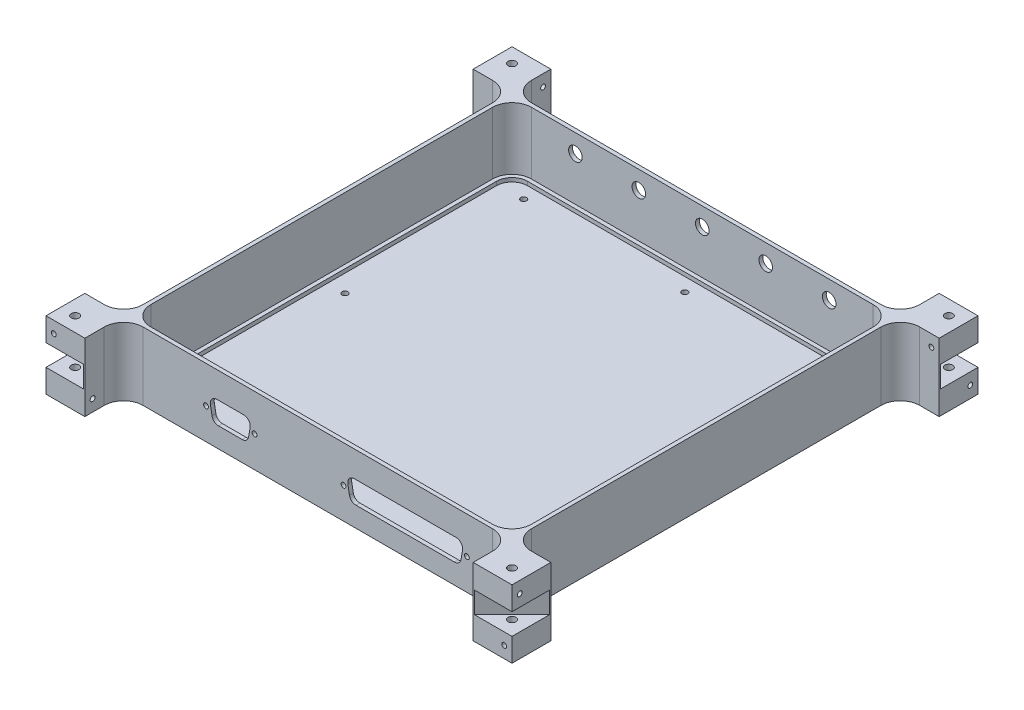
SolidWorks part; units mm, degrees
ref_plane "Front" through (0, 0, 0) normal (0, 0, 1) x (1, 0, 0)
ref_plane "Top" through (0, 0, 0) normal (0, 1, 0) x (1, 0, 0)
ref_plane "Right" through (0, 0, 0) normal (1, 0, 0) x (0, 0, -1)
sketch "Sketch1" plane through (0, 0, 0) normal (0, 1, 0) x (1, 0, 0)
  line L0 (-100, 90) -> (-100, -90)
  line L1 (-120, 120) -> (120, 120)
  line L2 (-120, 120) -> (-120, -120)
  line L3 (-120, -120) -> (120, -120)
  line L4 (120, 120) -> (120, -120)
  line L5 (-120, 120) -> (-100, 120)
  line L6 (-120, 120) -> (-120, 100)
  line L7 (-120, 100) -> (-110, 100)
  line L8 (-100, 120) -> (-100, 110)
  line L9 (-90, 100) -> (90, 100)
  line L10 (0, -24.5091) -> (0, 24.5091) construction
  line L11 (24.4282, 0) -> (-24.4282, 0) construction
  line L12 (100, 90) -> (100, -90)
  line L13 (100, 120) -> (100, 110)
  line L14 (120, 100) -> (110, 100)
  line L15 (120, 120) -> (120, 100)
  line L16 (120, 120) -> (100, 120)
  line L17 (120, -120) -> (100, -120)
  line L18 (120, -120) -> (120, -100)
  line L19 (120, -100) -> (110, -100)
  line L20 (100, -120) -> (100, -110)
  line L21 (-90, -100) -> (90, -100)
  line L22 (-100, -120) -> (-100, -110)
  line L23 (-120, -100) -> (-110, -100)
  line L24 (-120, -120) -> (-120, -100)
  line L25 (-120, -120) -> (-100, -120)
  line L26 (-120, -120) -> (120, -120)
  arc A0 (-100, 110) -> (-90, 100) centre (-90, 110) ccw
  arc A1 (-100, 90) -> (-110, 100) centre (-110, 90) ccw
  arc A2 (100, 90) -> (110, 100) centre (110, 90) cw
  arc A3 (100, 110) -> (90, 100) centre (90, 110) cw
  arc A4 (100, -110) -> (90, -100) centre (90, -110) ccw
  arc A5 (100, -90) -> (110, -100) centre (110, -90) ccw
  arc A6 (-100, -90) -> (-110, -100) centre (-110, -90) cw
  arc A7 (-100, -110) -> (-90, -100) centre (-90, -110) cw
  point P13 (0, -100)
  point P26 (0, 100)
  point P29 (0, 0)
  point P43 (100, 0)
  point P45 (-100, 0)
  dimension "D7" = 20
  dimension "D8" = 20
  dimension "D2" = 120
  dimension "D4" = 120
extrude "Boss-Extrude1" add sketch "Sketch1" along normal mid plane 35 contours L22 A7 L21 A4 L20 L3 L4 L19 A5 L12 A2 L14 L1 L13 A3 L9 A0 L8 L2 L7 A1 L0 A6 L23 region at (0, 0, 0)
sketch "Sketch2" plane through (0, 17.5, 0) normal (0, 1, 0) x (1, 0, 0)
  line L0 (-100, 90) -> (-100, -90) construction
  line L1 (-88, 98) -> (88, 98)
  line L2 (-98, 88) -> (-98, -88)
  line L3 (-88, -98) -> (88, -98)
  line L4 (98, 88) -> (98, -88)
  line L5 (-90, 100) -> (90, 100) construction
  line L6 (100, 90) -> (100, -90) construction
  line L7 (-90, -100) -> (90, -100) construction
  arc A0 (-98, -88) -> (-88, -98) centre (-88, -88) ccw
  arc A1 (88, -98) -> (98, -88) centre (88, -88) ccw
  arc A2 (88, 98) -> (98, 88) centre (88, 88) cw
  arc A3 (-88, 98) -> (-98, 88) centre (-88, 88) ccw
  dimension "D5" = 10
  dimension "D1" = 2
  dimension "D2" = 2
  dimension "D3" = 2
  dimension "D4" = 2
extrude "Cut-Extrude1" cut sketch "Sketch2" against normal blind 32
sketch "Sketch3" plane through (0, -14.5, 0) normal (0, 1, 0) x (1, 0, 0)
  line L8 (-88, -96) -> (88, -96)
  line L9 (96, -88) -> (96, 88)
  line L10 (88, 96) -> (-88, 96)
  line L11 (-96, 88) -> (-96, -88)
  line L12 (-88, -96) -> (88, -96)
  line L13 (96, -88) -> (96, 88)
  line L14 (88, 96) -> (-88, 96)
  line L15 (-96, 88) -> (-96, -88)
  arc A8 (-96, -88) -> (-88, -96) centre (-88, -88) ccw
  arc A9 (88, -96) -> (96, -88) centre (88, -88) ccw
  arc A10 (96, 88) -> (88, 96) centre (88, 88) ccw
  arc A11 (-88, 96) -> (-96, 88) centre (-88, 88) ccw
  arc A12 (-96, -88) -> (-88, -96) centre (-88, -88) ccw
  arc A13 (88, -96) -> (96, -88) centre (88, -88) ccw
  arc A14 (96, 88) -> (88, 96) centre (88, 88) ccw
  arc A15 (-88, 96) -> (-96, 88) centre (-88, 88) ccw
  dimension "D1" = 2
extrude "Cut-Extrude2" cut sketch "Sketch3" against normal blind 2
sketch "Sketch4" plane through (0, -17.5, 0) normal (0, -1, 0) x (1, 0, 0)
  line L24 (-88, -98) -> (88, -98)
  line L25 (98, -88) -> (98, 88)
  line L26 (88, 98) -> (-88, 98)
  line L27 (-98, 88) -> (-98, -88)
  line L28 (-88, -98) -> (88, -98)
  line L29 (98, -88) -> (98, 88)
  line L30 (88, 98) -> (-88, 98)
  line L31 (-98, 88) -> (-98, -88)
  arc A20 (-98, -88) -> (-88, -98) centre (-88, -88) ccw
  arc A21 (88, -98) -> (98, -88) centre (88, -88) ccw
  arc A22 (98, 88) -> (88, 98) centre (88, 88) ccw
  arc A23 (-88, 98) -> (-98, 88) centre (-88, 88) ccw
  arc A24 (-98, -88) -> (-88, -98) centre (-88, -88) ccw
  arc A25 (88, -98) -> (98, -88) centre (88, -88) ccw
  arc A26 (98, 88) -> (88, 98) centre (88, 88) ccw
  arc A27 (-88, 98) -> (-98, 88) centre (-88, 88) ccw
  dimension "D1" = 0
extrude "Boss-Extrude2" add sketch "Sketch4" along normal blind 2
ref_plane "Plane1" through (0, -5.5, 0) normal (0, 1, 0) x (1, 0, 0)
sketch "Sketch5" plane through (0, -5.5, 0) normal (0, 1, 0) x (1, 0, 0)
  line L0 (0, 0) -> (-112.0764, 112.0764)
  line L1 (0, 0) -> (-48.8177, 0)
  line L2 (-120, 100.6173) -> (-100.6173, 120)
  line L3 (-120, 120) -> (-120, 100) construction
  line L4 (-120, 120) -> (-100, 120) construction
  line L5 (-120, 100.6173) -> (-120, 120)
  line L6 (-120, 120) -> (-100.6173, 120)
  circle A0 centre (-112.0764, 112.0764) radius 2
  dimension "D3" = 4
  dimension "D1" = 158.5
  dimension "D2" = 45
  dimension "D4" = 2.5
  dimension "D5" = 135
ref_axis "Axis1" through (0, 0, 0) along (0, 1, 0)
extrude "Cut-Extrude3" cut sketch "Sketch5" along normal blind 11 contours L5 L6 L2
pattern_circular "CirPattern1" count 4 every 90 about axis through (0, 0, 0) along (0, 1, 0) of "Cut-Extrude3"
sketch "Sketch6" plane through (0, 17.5, 0) normal (0, 1, 0) x (1, 0, 0)
  line L0 (0, 0) -> (-143.5026, 143.5026) construction
  line L1 (-143.5026, 143.5026) -> (-143.5026, 0) construction
  line L2 (-143.5026, 0) -> (0, 0) construction
  line L3 (-120, 101.4521) -> (-101.4521, 120)
  line L4 (-120, 120) -> (-120, 100) construction
  line L5 (-120, 120) -> (-100, 120) construction
  circle A0 centre (-112.4938, 112.4938) radius 2
  dimension "D2" = 4
  dimension "D1" = 45
  dimension "D3" = 135
  dimension "D4" = 2.5
extrude "Cut-Extrude4" cut sketch "Sketch6" against normal through all contours A0 region at (-112.4938, 17.5, -112.4938)
pattern_circular "CirPattern2" count 4 every 90 about axis through (0, 0, 0) along (0, 1, 0) of "Cut-Extrude4"
sketch "Sketch7" plane through (120, 0, 0) normal (1, 0, 0) x (0, 0, -1)
  line L0 (-100, 17.5) -> (-120, 17.5) construction
  line L1 (-120, 17.5) -> (-120, 5.5) construction
  line L2 (120, -5.5) -> (120, -17.5) construction
  line L3 (120, -17.5) -> (100, -17.5) construction
  point P0 (-116, 11.5)
  point P1 (116, -11.5)
  dimension "D1" = 6
  dimension "D2" = 4
  dimension "D3" = 4
  dimension "D4" = 6
sketch "Sketch8" plane through (-120, 0, 0) normal (-1, 0, 0) x (0, 0, 1)
  line L0 (-120, 17.5) -> (-100, 17.5) construction
  line L1 (-120, 17.5) -> (-120, 5.5) construction
  line L2 (120, -5.5) -> (120, -17.5) construction
  line L3 (100, -17.5) -> (120, -17.5) construction
  point P0 (-116, 11.5)
  point P1 (116, -11.5)
  dimension "D1" = 6
  dimension "D2" = 4
  dimension "D3" = 4
  dimension "D4" = 6
sketch "Sketch9" plane through (0, 0, 120) normal (0, 0, 1) x (1, 0, 0)
  line L0 (-120, 17.5) -> (-120, 5.5) construction
  line L1 (-120, 17.5) -> (-100, 17.5) construction
  line L2 (120, -5.5) -> (120, -17.5) construction
  line L3 (100, -17.5) -> (120, -17.5) construction
  point P0 (-116, 11.5)
  point P1 (116, -11.5)
  dimension "D1" = 4
  dimension "D2" = 6
  dimension "D3" = 4
  dimension "D4" = 6
sketch "Sketch10" plane through (0, 0, -120) normal (0, 0, -1) x (-1, 0, 0)
  line L0 (-100, 17.5) -> (-120, 17.5) construction
  line L1 (-120, 17.5) -> (-120, 5.5) construction
  line L2 (120, -5.5) -> (120, -17.5) construction
  line L3 (120, -17.5) -> (100, -17.5) construction
  point P0 (-116, 11.5)
  point P1 (116, -11.5)
  dimension "D1" = 6
  dimension "D2" = 4
  dimension "D3" = 4
  dimension "D4" = 6
hole_wizard "Tap Drill for M3 Tap1" positions "3DSketch1" profile "Sketch12" hole size "M3" standard "AS" end condition up to next
sketch3d "3DSketch1"
  point P0 (116, 11.5, -120)
  point P3 (-116, -11.5, -120)
  point P6 (-120, 11.5, -116)
  point P9 (-120, -11.5, 116)
  point P12 (-116, 11.5, 120)
  point P15 (116, -11.5, 120)
  point P18 (120, 11.5, 116)
  point P21 (120, -11.5, -116)
sketch "Sketch12" plane through (116, 11.5, -120) normal (1, 0, 0) x (0, 1, 0)
  line L0 (0, 0) -> (0, 20)
  line L1 (0, 20) -> (1.25, 20)
  line L2 (1.25, 20) -> (1.25, 0)
  line L5 (1.25, 0) -> (0, 0)
  line L11 (0, -6.35) -> (0, 107.95) construction
  dimension "Thru Hole Dia." = 2.5
  dimension "Thru Hole Depth" = 20
sketch "Sketch13" plane through (0, -16.5, 0) normal (0, 1, 0) x (1, 0, 0)
  line L0 (-96, 0) -> (96, 0) construction
  line L1 (-96, 88) -> (-96, -88) construction
  line L2 (96, -88) -> (96, 88) construction
  line L3 (0, -96) -> (0, 96) construction
  line L4 (-88, -96) -> (88, -96) construction
  line L5 (88, 96) -> (-88, 96) construction
  point P12 (-83, 89)
  point P13 (0, 89)
  point P14 (83, 89)
  point P15 (87, 1)
  point P16 (-87, 1)
  point P17 (-87, -87)
  point P18 (87, -87)
  point P19 (0, -87)
  dimension "D1" = 83
  dimension "D2" = 83
  dimension "D3" = 89
  dimension "D4" = 89
  dimension "D5" = 89
  dimension "D6" = 1
  dimension "D7" = 1
  dimension "D8" = 87
  dimension "D9" = 87
  dimension "D10" = 87
  dimension "D11" = 87
  dimension "D12" = 87
hole_wizard "Ø3.0 (3) Diameter Hole1" positions "Sketch15" profile "Sketch14" hole size "Ø3.0" standard "AS"
sketch "Sketch15" plane through (0, 0, 0) normal (0, 1, 0) x (1, 0, 0)
  point P0 (-83, 89)
  point P3 (0, 89)
  point P6 (83, 89)
  point P9 (87, 1)
  point P12 (-87, 1)
  point P15 (-87, -87)
  point P18 (0, -87)
  point P21 (87, -87)
sketch "Sketch14" plane through (-83, 0, -89) normal (1, 0, 0) x (0, 0, 1)
  line L0 (0, 0) -> (0, 20.9013)
  line L1 (0, 20.9013) -> (1.5, 20)
  line L2 (1.5, 20) -> (1.5, 0)
  line L5 (1.5, 0) -> (0, 0)
  line L10 (0, 20.9013) -> (-1.5, 20) construction
  line L11 (0, -6.35) -> (0, 107.95) construction
  dimension "Hole Dia." = 3
  dimension "Hole Depth" = 20
  dimension "Drill Angle" = 118
sketch "Sketch16" plane through (0, 0, -100) normal (0, 0, -1) x (-1, 0, 0)
  line L0 (0, 0) -> (0, 8.1) construction
  circle A0 centre (0, 8.1) radius 3.5
  circle A1 centre (32.67, 8.1) radius 3.5
  circle A2 centre (65.34, 8.1) radius 3.5
  circle A3 centre (-32.67, 8.1) radius 3.5
  circle A4 centre (-65.34, 8.1) radius 3.5
  dimension "D2" = 7
  dimension "D5" = 7
  dimension "D6" = 7
  dimension "D8" = 7
  dimension "D9" = 7
  dimension "D1" = 8.1
  dimension "D3" = 32.67
  dimension "D4" = 32.67
  dimension "D7" = 32.67
  dimension "D10" = 32.67
extrude "Cut-Extrude5" cut sketch "Sketch16" against normal up to next
sketch "Sketch17" plane through (0, 0, 100) normal (0, 0, 1) x (1, 0, 0)
  line L0 (-51.9767, 4.23) -> (-38.2033, 4.23)
  line L1 (-34.855, 0.2396) -> (-35.6661, -4.3604)
  line L2 (-39.0145, -7.17) -> (-51.1655, -7.17)
  line L3 (-54.5139, -4.3604) -> (-55.325, 0.2396)
  line L4 (16.2711, -4.3604) -> (15.46, 0.2396)
  line L5 (120, 5.5) -> (120, -5.5) construction
  line L7 (-90, 17.5) -> (90, 17.5) construction
  line L8 (-120, 17.5) -> (-120, 5.5) construction
  line L9 (18.8083, 4.23) -> (71.1917, 4.23)
  line L10 (74.54, 0.2396) -> (73.7289, -4.3604)
  line L11 (70.3805, -7.17) -> (19.6195, -7.17)
  arc A0 (-38.2033, 4.23) -> (-34.855, 0.2396) centre (-38.2033, 0.83) cw
  arc A1 (-35.6661, -4.3604) -> (-39.0145, -7.17) centre (-39.0145, -3.77) cw
  arc A2 (-51.1655, -7.17) -> (-54.5139, -4.3604) centre (-51.1655, -3.77) cw
  arc A3 (-55.325, 0.2396) -> (-51.9767, 4.23) centre (-51.9767, 0.83) cw
  arc A4 (71.1917, 4.23) -> (74.54, 0.2396) centre (71.1917, 0.83) cw
  arc A5 (73.7289, -4.3604) -> (70.3805, -7.17) centre (70.3805, -3.77) cw
  arc A6 (19.6195, -7.17) -> (16.2711, -4.3604) centre (19.6195, -3.77) cw
  arc A7 (15.46, 0.2396) -> (18.8083, 4.23) centre (18.8083, 0.83) cw
  dimension "D1" = 3.4
  dimension "D2" = 3.4
  dimension "D3" = 3.4
  dimension "D4" = 3.4
  dimension "D12" = 3.4
  dimension "D13" = 3.4
  dimension "D14" = 3.4
  dimension "D15" = 3.4
  dimension "D5" = 11.4
  dimension "D6" = 80
  dimension "D7" = 80
  dimension "D8" = 20.47
  dimension "D9" = 13.27
  dimension "D10" = 64.675
  dimension "D11" = 11.4
  dimension "D16" = 80
  dimension "D17" = 80
  dimension "D18" = 59.08
  dimension "D19" = 13.27
  dimension "D20" = 45.46
extrude "Cut-Extrude6" cut sketch "Sketch17" against normal blind 10
hole_wizard "M3x0.5 Tapped Hole1" positions "Sketch19" profile "Sketch18" tap size "M3x0.5" standard "ANSI Metric"
sketch "Sketch19" plane through (0, 0, 100) normal (0, 0, 1) x (1, 0, 0)
  line L0 (-38.2033, 4.23) -> (-51.9767, 4.23) construction
  line L1 (71.1917, 4.23) -> (18.8083, 4.23) construction
  point P0 (-57.585, -1.47)
  point P2 (-32.595, -1.47)
  point P4 (13.25, -1.47)
  point P6 (76.75, -1.47)
  dimension "D1" = 5.7
  dimension "D2" = 5.7
  dimension "D3" = 2.26
  dimension "D4" = 2.26
  dimension "D5" = 5.7
  dimension "D6" = 5.7
  dimension "D7" = 2.21
  dimension "D8" = 2.21
sketch "Sketch18" plane through (-57.585, -1.47, 100) normal (1, 0, 0) x (0, -1, 0)
  line L0 (0, 0) -> (0, 5.7511)
  line L1 (0, 5.7511) -> (1.25, 5)
  line L2 (1.25, 5) -> (1.25, 0)
  line L5 (1.25, 0) -> (0, 0)
  line L10 (0, 5.7511) -> (-1.25, 5) construction
  line L11 (0, -6.35) -> (0, 107.95) construction
  dimension "Tap Drill Dia." = 2.5
  dimension "Tap Drill Depth" = 5
  dimension "Drill Angle" = 118
cosmetic thread "Hole Thread1" parameters "D1"=2, "D2"=3
cosmetic thread "Hole Thread2" parameters "D1"=2, "D2"=3
cosmetic thread "Hole Thread3" parameters "D1"=2, "D2"=3
cosmetic thread "Hole Thread4" parameters "D1"=2, "D2"=3
